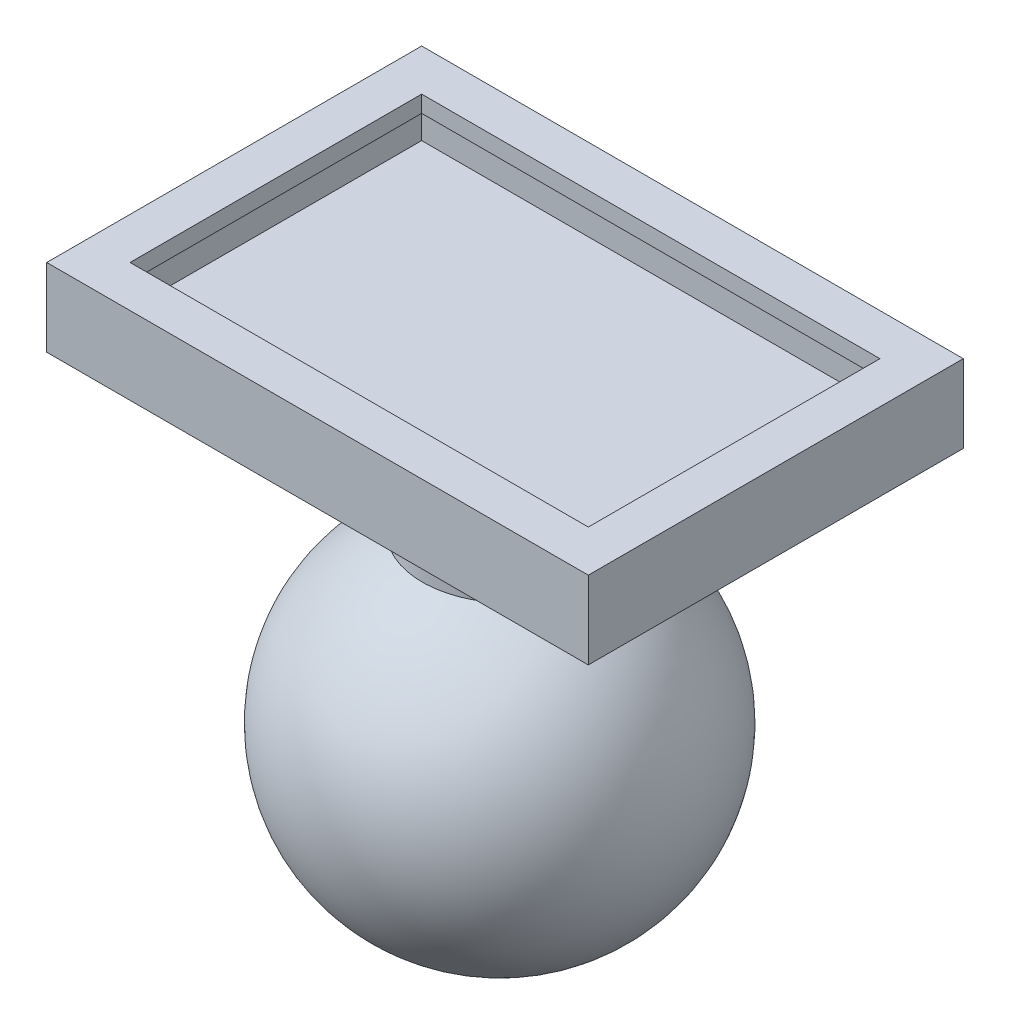
SolidWorks part; units mm, degrees
ref_plane "Plan de face" through (0, 0, 0) normal (0, 0, 1) x (1, 0, 0)
ref_plane "Plan de dessus" through (0, 0, 0) normal (0, 1, 0) x (1, 0, 0)
ref_plane "Plan de droite" through (0, 0, 0) normal (1, 0, 0) x (0, 0, -1)
sketch "Esquisse1" plane through (0, 0, 0) normal (0, 1, 0) x (1, 0, 0)
  line L1 (0, 0) -> (33, 0)
  line L2 (0, 0) -> (0, 21)
  line L3 (0, 21) -> (33, 21)
  line L4 (33, 0) -> (33, 21)
  line L5 (-3, 24) -> (36, 24)
  line L6 (-3, 24) -> (-3, -3)
  line L7 (-3, -3) -> (36, -3)
  line L8 (36, 24) -> (36, -3)
  dimension "D1" = 33
  dimension "D2" = 39
  dimension "D3" = 3
  dimension "D4" = 3
  dimension "D5" = 21
  dimension "D6" = 27
  dimension "D7" = 3
extrude "Boss.-Extru.1" add sketch "Esquisse1" along normal blind 1.2
sketch "Esquisse2" plane through (0, 0, 0) normal (0, -1, 0) x (-1, 0, 0)
  line L0 (0, 0) -> (-33, 0) construction
  line L1 (3, -3) -> (-36, -3)
  line L2 (3, -3) -> (3, 24)
  line L3 (3, 24) -> (-36, 24)
  line L4 (-36, -3) -> (-36, 24)
  line L5 (1.5, -1.5) -> (-34.5, -1.5)
  line L6 (1.5, -1.5) -> (1.5, 22.5)
  line L7 (1.5, 22.5) -> (-34.5, 22.5)
  line L8 (-34.5, -1.5) -> (-34.5, 22.5)
  line L9 (-33, 21) -> (0, 21) construction
  line L10 (0, 21) -> (0, 0) construction
  dimension "D1" = 1.5
  dimension "D2" = 1.5
  dimension "D3" = 1.5
  dimension "D4" = 1.5
extrude "Boss.-Extru.3" add sketch "Esquisse2" along normal blind 3.2
sketch "Esquisse3" plane through (0, -3.2, 0) normal (0, -1, 0) x (-1, 0, 0)
  line L1 (3, -3) -> (-36, -3)
  line L2 (3, -3) -> (3, 24)
  line L3 (3, 24) -> (-36, 24)
  line L4 (-36, -3) -> (-36, 24)
extrude "Boss.-Extru.4" add sketch "Esquisse3" along normal blind 1.2
sketch "Esquisse5" plane through (0, -4.4, 0) normal (0, -1, 0) x (-1, 0, 0)
  line L0 (-36, -3) -> (3, -3) construction
  line L1 (3, 24) -> (-36, 24) construction
  line L2 (-36, 24) -> (-36, -3) construction
  line L3 (3, -3) -> (3, 24) construction
  circle A0 centre (-16.5, 10.5) radius 6
  dimension "D1" = 13.5
  dimension "D2" = 13.5
  dimension "D3" = 19.5
  dimension "D4" = 19.5
extrude "Boss.-Extru.6" add sketch "Esquisse5" along normal blind 20
sketch "Esquisse6" plane through (0, -4.4, 0) normal (0, -1, 0) x (1, 0, 0)
  line L0 (-3, 3) -> (-3, -24) construction
  line L1 (-3, -24) -> (36, -24) construction
  circle A0 centre (16.5, -10.5) radius 7.123
  point P6 (-14.2262, 4.9852)
  dimension "D1" = 19.5
  dimension "D2" = 13.5
extrude "Boss.-Extru.7" add sketch "Esquisse6" along normal blind 1.5
fillet "Congé1" radius 1.2 1 edges at (16.5, -5.9, -17.623)
sketch "Esquisse7" plane through (0, -24.4, 0) normal (0, -1, 0) x (1, 0, 0)
  line L0 (3.6334, -7.8413) -> (29.2038, -12.5483)
  arc A0 (3.6334, -7.8413) -> (29.2038, -12.5483) centre (16.4186, -10.1948) ccw
  dimension "D1" = 13
revolve "Révolution2" add sketch "Esquisse7" angle 360 about L0
